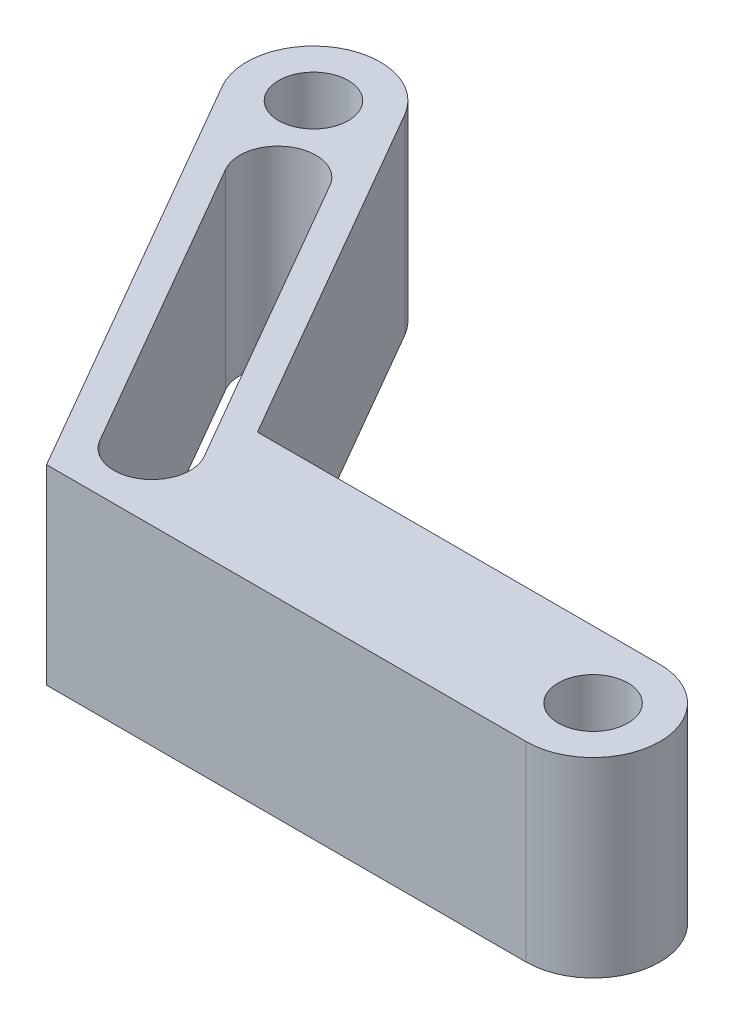
SolidWorks part; units mm, degrees
material "ABS"
ref_plane "Ebene vorne" through (0, 0, 0) normal (0, 0, 1) x (1, 0, 0)
ref_plane "Ebene oben" through (0, 0, 0) normal (0, 1, 0) x (1, 0, 0)
ref_plane "Ebene rechts" through (0, 0, 0) normal (1, 0, 0) x (0, 0, -1)
sketch "Skizze2" plane through (0, 0, 0) normal (0, 1, 0) x (1, 0, 0)
  line L1 (0, 3.5) -> (-21.0733, 3.5)
  line L2 (-21.0733, 3.5) -> (-31.6099, 21.75)
  line L4 (-37.6721, 18.25) -> (-25.1147, -3.5)
  line L5 (-25.1147, -3.5) -> (0, -3.5)
  line L6 (0, 0) -> (-23.094, 0) construction
  line L7 (-34.641, 20) -> (-23.094, 0) construction
  line L8 (-34.641, 20) -> (0, 0) construction
  arc A4 (0, 3.5) -> (0, -3.5) centre (0, 0) cw
  arc A5 (-31.6099, 21.75) -> (-37.6721, 18.25) centre (-34.641, 20) ccw
  circle A6 centre (-34.641, 20) radius 1.825
  circle A7 centre (0, 0) radius 1.825
  dimension "D3" = 40
  dimension "D4" = 60
  dimension "D5" = 3.65
  dimension "D6" = 3.65
  dimension "D1" = 7
  dimension "D2" = 7
extrude "Aufsatz-Linear austragen1" add sketch "Skizze2" along normal blind 10
sketch "Skizze3" plane through (0, 10, 0) normal (0, 1, 0) x (1, 0, 0)
  line L0 (0, 0) -> (-34.641, 20) construction
sketch "Skizze4" plane through (0, 10, 0) normal (0, 1, 0) x (1, 0, 0)
  line L0 (-32.094, 15.5885) -> (-23.094, 0) construction
  line L1 (-30.362, 16.5885) -> (-21.362, 1)
  line L2 (-33.8261, 14.5885) -> (-24.8261, -1)
  line L3 (-21.0733, 3.5) -> (-31.6099, 21.75) construction
  line L4 (-37.6721, 18.25) -> (-25.1147, -3.5) construction
  arc A0 (-30.362, 16.5885) -> (-33.8261, 14.5885) centre (-32.094, 15.5885) ccw
  arc A1 (-24.8261, -1) -> (-21.362, 1) centre (-23.094, 0) ccw
  point P2 (-27.594, 7.7942)
  dimension "D1" = 18
  dimension "D2" = 4
extrude "Schnitt-Linear austragen1" cut sketch "Skizze4" against normal through all
